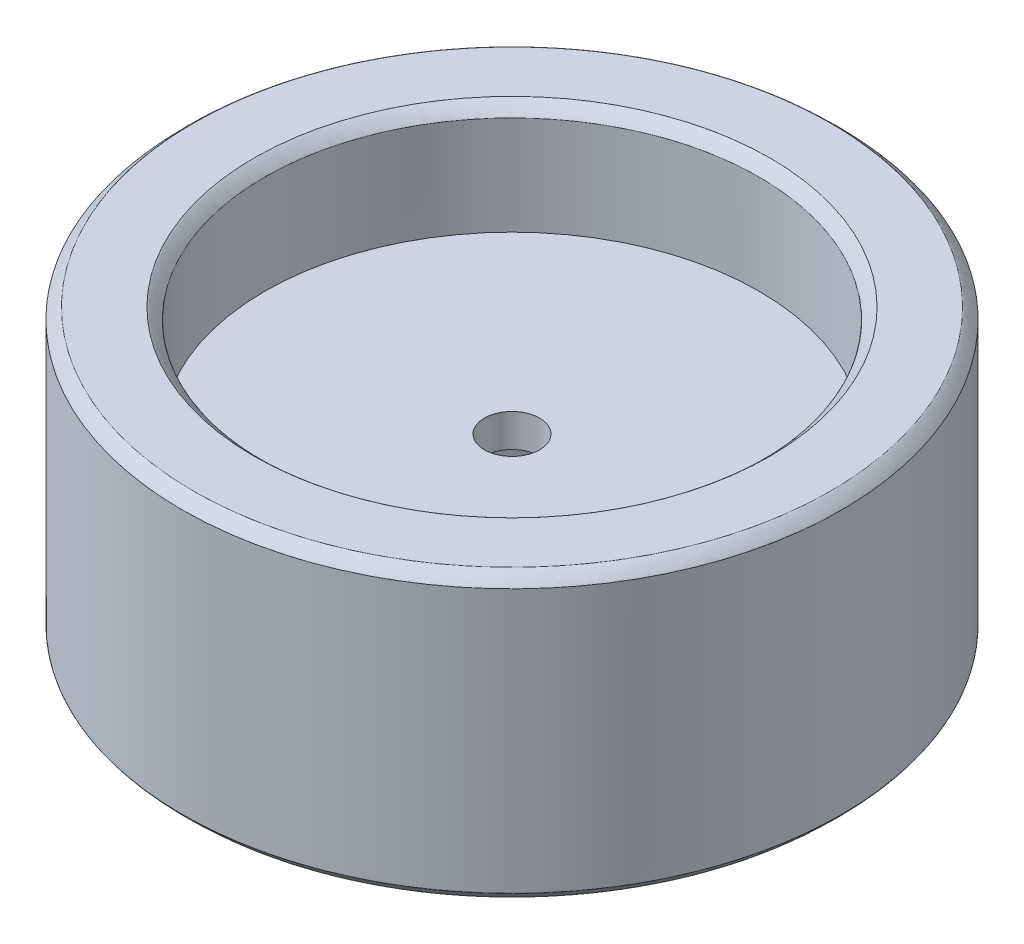
SolidWorks part; units mm, degrees
ref_plane "Front Plane" through (0, 0, 0) normal (0, 0, 1) x (1, 0, 0)
ref_plane "Top Plane" through (0, 0, 0) normal (0, 1, 0) x (1, 0, 0)
ref_plane "Right Plane" through (0, 0, 0) normal (1, 0, 0) x (0, 0, -1)
other "Configuration Table"
sketch "Sketch1" plane through (0, 0, 0) normal (0, 1, 0) x (1, 0, 0)
  line L1 (6.9282, 0) -> (3.4641, 6)
  line L2 (3.4641, 6) -> (-3.4641, 6)
  line L3 (-3.4641, 6) -> (-6.9282, 0)
  line L4 (-6.9282, 0) -> (-3.4641, -6)
  line L5 (-3.4641, -6) -> (3.4641, -6)
  line L6 (3.4641, -6) -> (6.9282, 0)
  circle A1 centre (0, 0) radius 30
  circle A3 centre (0, 0) radius 6 construction
  circle A4 centre (0, 0) radius 8
  circle A5 centre (0, 0) radius 2.51
  circle A6 centre (0, 0) radius 22.5
  dimension "D1" = 12
  dimension "D2" = 60
  dimension "D3" = 45
  dimension "D4" = 16
  dimension "D5" = 5.02
extrude "Boss-Extrude2" add sketch "Sketch1" along normal blind 26 contours A1
extrude "Cut-Extrude3" cut sketch "Sketch1<4>" along normal blind 13 contours A6
sketch "Sketch1<4>" plane through (0, 0, 0) normal (0, 1, 0) x (1, 0, 0) same geometry as "Sketch1"
extrude "Boss-Extrude3" add sketch "Sketch1<5>" along normal blind 13 contours A4
sketch "Sketch1<5>" plane through (0, 0, 0) normal (0, 1, 0) x (1, 0, 0) same geometry as "Sketch1"
extrude "Cut-Extrude4" cut sketch "Sketch1<6>" along normal blind 9 contours A4
sketch "Sketch1<6>" plane through (0, 0, 0) normal (0, 1, 0) x (1, 0, 0) same geometry as "Sketch1"
extrude "Cut-Extrude5" cut sketch "Sketch1<7>" along normal blind 13 contours L5 L6 L1 L2 L3 L4
sketch "Sketch1<7>" plane through (0, 0, 0) normal (0, 1, 0) x (1, 0, 0) same geometry as "Sketch1"
extrude "Cut-Extrude6" cut sketch "Sketch1<8>" along normal blind 31 contours A5
sketch "Sketch1<8>" plane through (0, 0, 0) normal (0, 1, 0) x (1, 0, 0) same geometry as "Sketch1"
sketch "Sketch2" plane through (0, 26, 0) normal (0, 1, 0) x (1, 0, 0)
  circle A0 centre (0, 0) radius 22.5
extrude "Cut-Extrude7" cut sketch "Sketch2" against normal blind 10 contours A0
fillet "Fillet1" radius 1 4 edges at (0, 26, 22.5) (0, 26, 30) (0, 0, 22.5) (0, 0, 30) conic radius 10
